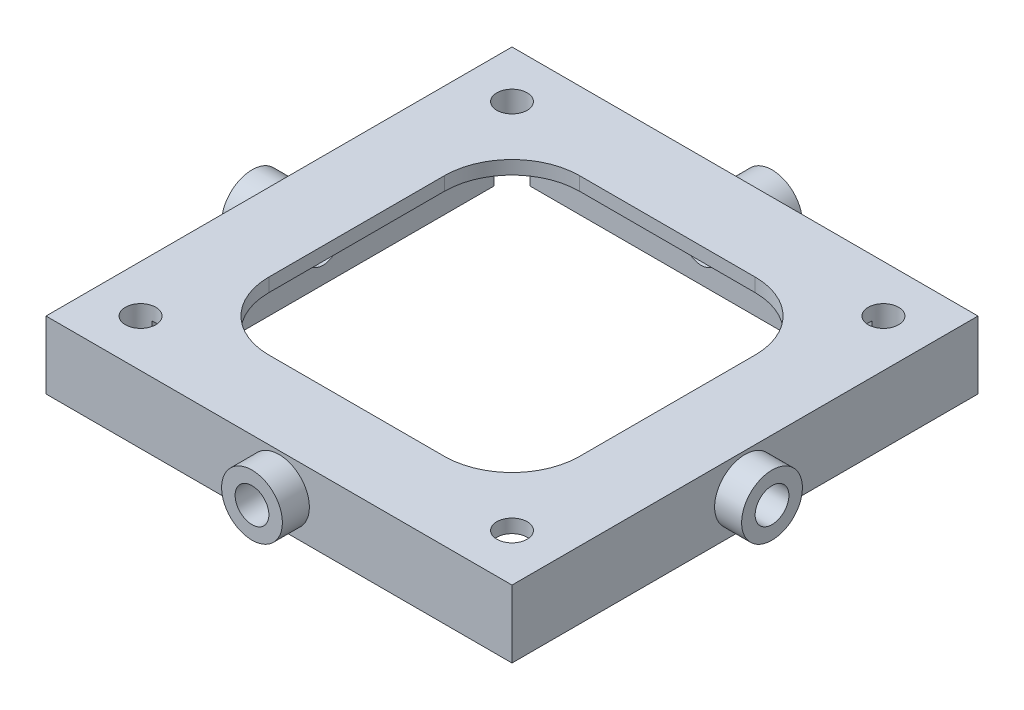
SolidWorks part; units mm, degrees
ref_plane "Front Plane" through (0, 0, 0) normal (0, 0, 1) x (1, 0, 0)
ref_plane "Top Plane" through (0, 0, 0) normal (0, 1, 0) x (1, 0, 0)
ref_plane "Right Plane" through (0, 0, 0) normal (1, 0, 0) x (0, 0, -1)
other "Center of Mass"
sketch "Sketch6" plane through (0, 0, 0) normal (0, 1, 0) x (1, 0, 0)
  line L5 (34.5, 34.5) -> (-34.5, 34.5)
  line L6 (34.5, 34.5) -> (34.5, -34.5)
  line L11 (34.5, -34.5) -> (-34.5, -34.5)
  line L12 (-34.5, 34.5) -> (-34.5, -34.5)
  line L13 (34.5, 34.5) -> (-34.5, -34.5) construction
  line L14 (34.5, -34.5) -> (-34.5, 34.5) construction
  point P0 (0, 0)
extrude "Boss-Extrude1" add sketch "Sketch6" against normal blind 10
sketch "Sketch5" plane through (0, 0, 0) normal (0, 1, 0) x (1, 0, 0)
  circle A2 centre (27.5, 27.5) radius 2.25
  circle A3 centre (27.5, -27.5) radius 2.25
  circle A4 centre (-27.5, -27.5) radius 2.25
  circle A5 centre (-27.5, 27.5) radius 2.25
extrude "Cut-Extrude1" cut sketch "Sketch5" against normal through all both and the other way through all
sketch "Sketch7" plane through (0, 0, 0) normal (0, 1, 0) x (1, 0, 0)
  line L1 (-28, -28) -> (28, -28)
  line L2 (-28, -28) -> (-28, 28)
  line L3 (-28, 28) -> (28, 28)
  line L4 (28, -28) -> (28, 28)
  line L5 (-28, -28) -> (28, 28) construction
  line L6 (-28, 28) -> (28, -28) construction
  point P0 (0, 0)
  point P6 (-26.1357, -26.5875)
  point P7 (27.7076, 28.0835)
extrude "Cut-Extrude2" cut sketch "Sketch7" against normal blind 10 from offset 2 offset against normal yes
sketch "Sketch9" plane through (0, 0, 0) normal (0, 1, 0) x (1, 0, 0)
  line L1 (-23, -23) -> (23, -23)
  line L2 (-23, -23) -> (-23, 23)
  line L3 (-23, 23) -> (23, 23)
  line L4 (23, -23) -> (23, 23)
  line L5 (-23, -23) -> (23, 23) construction
  line L6 (-23, 23) -> (23, -23) construction
  point P0 (0, 0)
extrude "Cut-Extrude3" cut sketch "Sketch9" against normal through all both and the other way through all
fillet "Fillet1" radius 10 4 edges at (-23, -1, -23) (-23, -1, 23) (23, -1, -23) (23, -1, 23)
sketch "Sketch10" plane through (0, 0, -34.5) normal (0, 0, -1) x (-1, 0, 0)
  line L0 (103.5, 10) -> (-34.5, -10) construction
  line L1 (-34.5, 0) -> (34.5, -10) construction
  circle A0 centre (0, -5) radius 4.5
  point P5 (34.5, 0)
  point P12 (0, 0)
extrude "Boss-Extrude2" add sketch "Sketch10" along normal blind 4
ref_point "Point1"
ref_plane "Plane1" through (0, 0, -38.5) normal (0, 0, -1) x (-1, 0, 0)
sketch "Sketch11" plane through (0, 0, -38.5) normal (0, 0, -1) x (-1, 0, 0)
  circle A0 centre (0, -5) radius 2.5
extrude "Cut-Extrude4" cut sketch "Sketch11" against normal up to next
sketch "Sketch12" plane through (0, -10, 0) normal (0, -1, 0) x (-1, 0, 0)
  line L1 (-4.6474, 32.939) -> (4.6474, 32.939)
  line L2 (-4.6474, 32.939) -> (-4.6474, 29.439)
  line L3 (-4.6474, 29.439) -> (4.6474, 29.439)
  line L4 (4.6474, 32.939) -> (4.6474, 29.439)
  line L5 (-4.6474, 32.939) -> (4.6474, 29.439) construction
  line L6 (-4.6474, 29.439) -> (4.6474, 32.939) construction
  point P0 (0, 31.189)
  point P5 (0, 0)
extrude "Cut-Extrude5" cut sketch "Sketch12" against normal offset from surface (9 mm away) 1 up to face at (0, 0, 0)
ref_axis "Axis1" through (0, 0, 0) along (0, 1, 0)
pattern_circular "CirPattern1" count 4 every 90 about axis through (0, 0, 0) along (0, 1, 0) of "Boss-Extrude2", "Cut-Extrude5", "Cut-Extrude4"
